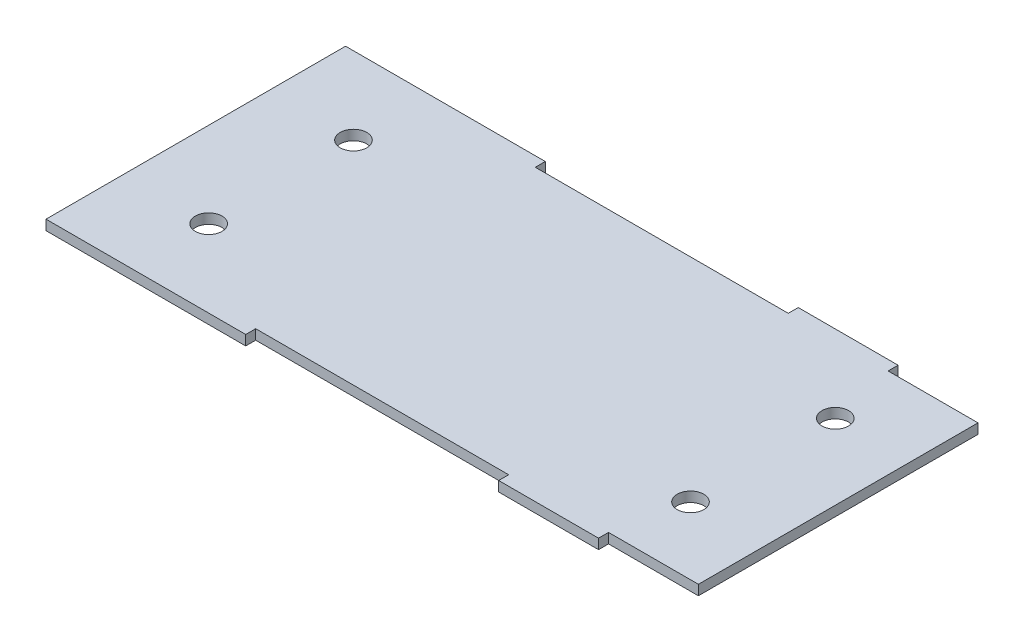
SolidWorks part; units mm, degrees
ref_plane "Front Plane" through (0, 0, 0) normal (0, 0, 1) x (1, 0, 0)
ref_plane "Top Plane" through (0, 0, 0) normal (0, 1, 0) x (1, 0, 0)
ref_plane "Right Plane" through (0, 0, 0) normal (1, 0, 0) x (0, 0, -1)
sketch "Sketch1" plane through (0, 0, 0) normal (0, 1, 0) x (1, 0, 0)
  line L0 (38, 45) -> (38, 42)
  line L1 (-98, -45) -> (98, -45)
  line L2 (-98, -45) -> (-98, 45)
  line L3 (-98, 45) -> (98, 45)
  line L4 (98, -45) -> (98, 45)
  line L5 (-98, -45) -> (98, 45) construction
  line L6 (-98, 45) -> (98, -45) construction
  line L7 (38, 42) -> (-38, 42)
  line L8 (-38, 42) -> (-38, 45)
  line L9 (98, 42) -> (68, 42)
  line L10 (68, 42) -> (68, 45)
  line L11 (95, -45) -> (95, 45)
  line L15 (-38, -45) -> (-38, -42)
  line L16 (-38, -42) -> (38, -42)
  line L17 (38, -42) -> (38, -45)
  line L18 (38, -45) -> (68, -45)
  line L19 (68, -45) -> (68, -42)
  line L20 (68, -42) -> (98, -42)
  circle A0 centre (72.375, -21.75) radius 4
  circle A1 centre (72.375, 21.75) radius 4
  circle A2 centre (-72.375, 21.75) radius 4
  circle A3 centre (-72.375, -21.75) radius 4
  point P0 (0, 0)
  dimension "D7" = 8
  dimension "D10" = 8
  dimension "D18" = 8
  dimension "D19" = 8
  dimension "D1" = 196
  dimension "D2" = 90
  dimension "D3" = 30
  dimension "D4" = 30
  dimension "D5" = 60
  dimension "D6" = 3
  dimension "D8" = 30
  dimension "D9" = 30
  dimension "D11" = 3
  dimension "D12" = 3
  dimension "D13" = 3
  dimension "D14" = 22.625
  dimension "D15" = 22.625
  dimension "D16" = 23.25
  dimension "D17" = 23.25
  dimension "D20" = 23.25
  dimension "D21" = 23.25
  dimension "D22" = 25.625
  dimension "D23" = 25.625
extrude "Boss-Extrude1" add sketch "Sketch1" along normal blind 3 contours L19 L20 L11 L9 L10 L3 L0 L7 L8 L2 L1 L15 L16 L17 A3 A2 A1 A0 region at (-2.372, 0, 0)
